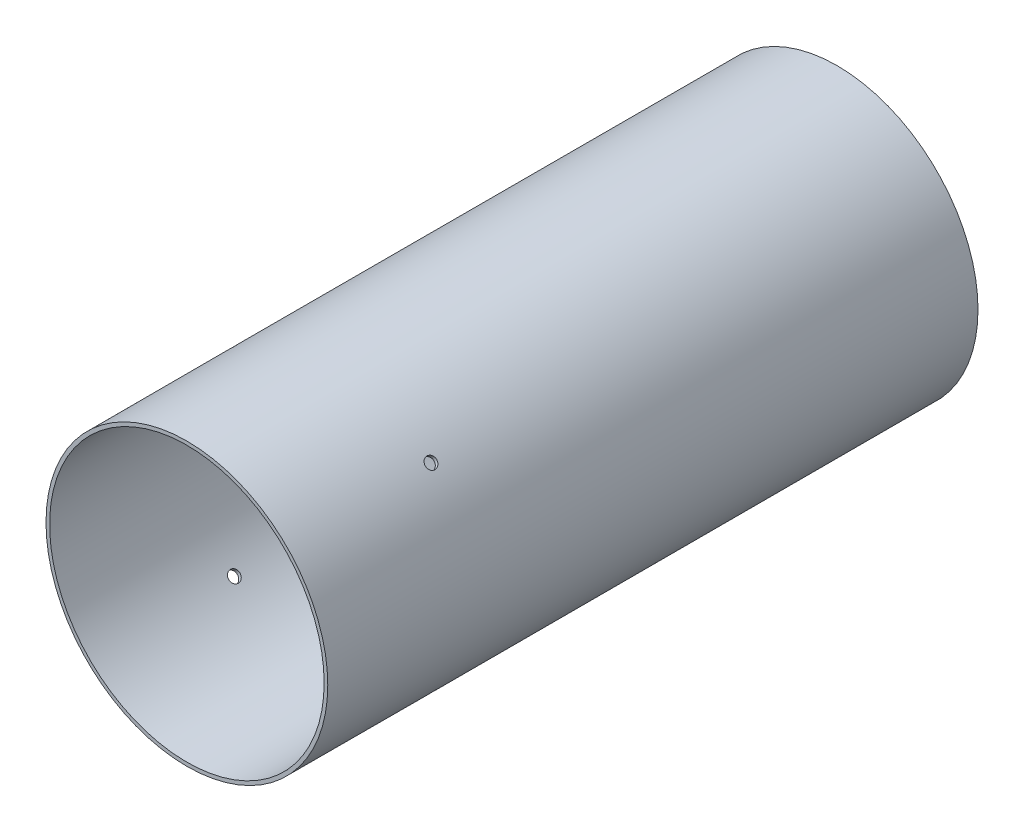
SolidWorks part; units mm, degrees
ref_plane "Front Plane" through (0, 0, 0) normal (0, 0, 1) x (1, 0, 0)
ref_plane "Top Plane" through (0, 0, 0) normal (0, 1, 0) x (1, 0, 0)
ref_plane "Right Plane" through (0, 0, 0) normal (1, 0, 0) x (0, 0, -1)
sketch "Sketch1" plane through (0, 0, 0) normal (0, 0, 1) x (1, 0, 0)
  circle A0 centre (0, 0) radius 49.53
  circle A1 centre (0, 0) radius 48.26
  dimension "D1" = 99.06
  dimension "D2" = 96.52
extrude "Boss-Extrude1" add sketch "Sketch1" along normal blind 228.6
extrude "Cut-Extrude1" cut sketch "Sketch2" against normal blind 12.7
sketch "Sketch2" plane through (-120.5803, -48.7382, -78.9954) normal (-0.7071, 0.7071, 0) x (0.7071, 0.7071, 0)
  circle A0 centre (119.7263, -256.7954) radius 1.9844
  point P2 (0, 0)
  point P3 (0, 0)
  point P6 (0, 0)
pattern_circular "CirPattern1" count 4 over 360 of "Cut-Extrude1"
